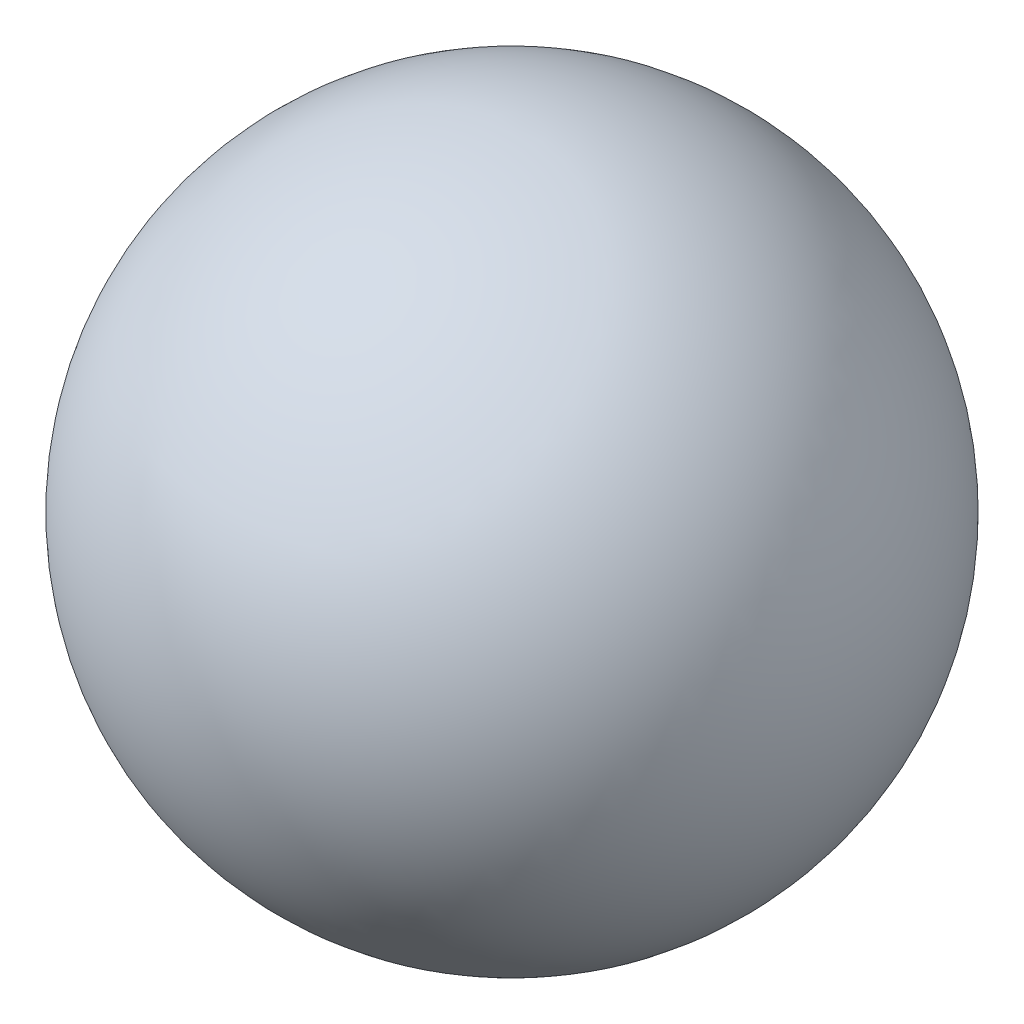
SolidWorks part; units mm, degrees
note: '?' marks a value the reader was unsure of.
ref_plane "Front Plane" through (0, 0, 0) normal (0, 0, 1) x (1, 0, 0)
ref_plane "Top Plane" through (0, 0, 0) normal (0, 1, 0) x (1, 0, 0)
ref_plane "Right Plane" through (0, 0, 0) normal (1, 0, 0) x (0, 0, -1)
sketch "Sketch1" plane through (0, 0, 0) normal (0, 0, 1) x (1, 0, 0)
  line L0 (0, -38.1) -> (0, 38.1) construction
  arc A0 (0, -38.1) -> (0, 38.1) centre (0, 0) ccw
  point P7 (0, 0)
  dimension "D1" = 38.1
revolve "Revolve-Thin1" add sketch "Sketch1" angle 360 about L0
sketch "Sketch2" plane through (0, 0, 0) normal (0, 0, 1) x (1, 0, 0)
  circle A0 centre (-63.5, 0) radius 50
  circle A1 centre (0, 0) radius 63.5 construction
  circle A2 centre (63.5, 0) radius 50
  dimension "D1" = 100
ref_axis "Axis1" through (69.8478, 0, 0) along (-1, 0, 0)?
ref_axis "Axis2" through (0, 69.8478, 0) along (0, -1, 0)?
ref_axis "Axis3" through (0, 0, -285.9471) along (0, 0, 1)?
ref_plane "Plane1" through (-320, 0, 0) normal (1, 0, 0) x (0, 0, -1)
sketch "Sketch7" plane through (-320, 0, 0) normal (1, 0, 0) x (0, 0, -1)
  line L0 (-206.4028, 15) -> (206.4028, 15) construction
  text T0 "basketball" font "Century Gothic" height 45
  point P2 (0, 15)
  dimension "D1" = 15
